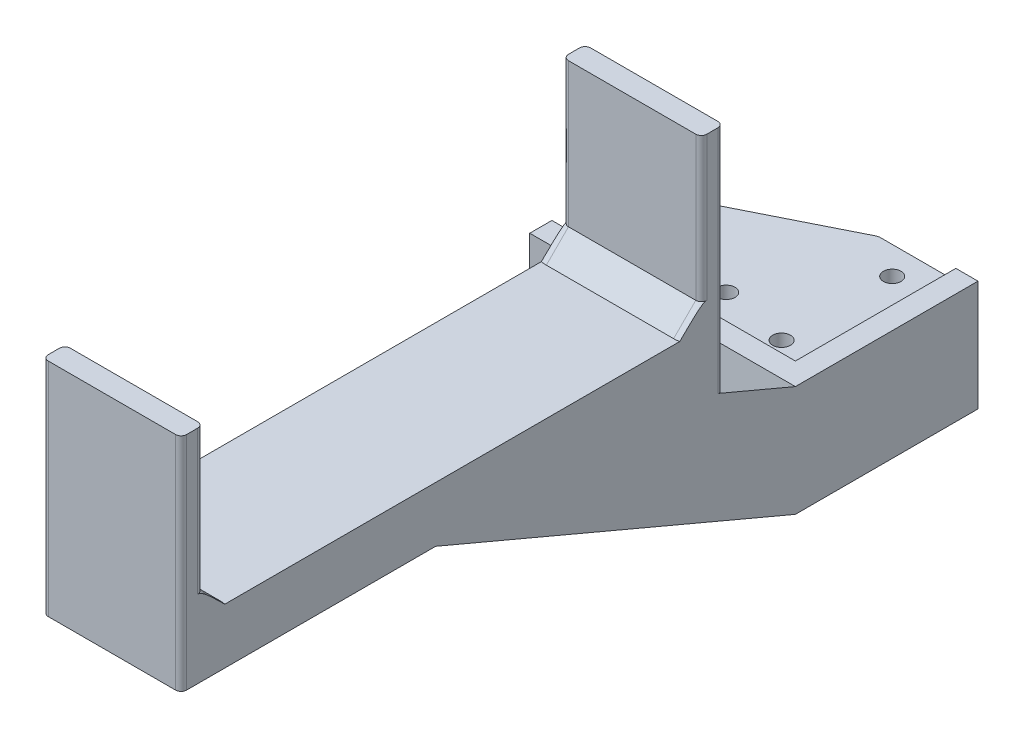
SolidWorks part; units mm, degrees
ref_plane "正面" through (0, 0, 0) normal (0, 0, 1) x (1, 0, 0)
ref_plane "平面" through (0, 0, 0) normal (0, 1, 0) x (1, 0, 0)
ref_plane "右側面" through (0, 0, 0) normal (1, 0, 0) x (0, 0, -1)
sketch "ｽｹｯﾁ1" plane through (0, 0, 0) normal (0, 1, 0) x (1, 0, 0)
  line L0 (7.5, 30) -> (7.5, 0) construction
  line L1 (0, 0) -> (15, 0)
  line L2 (0, 0) -> (0, 30)
  line L3 (0, 30) -> (15, 30)
  line L4 (15, 0) -> (15, 30)
  line L5 (0, 0) -> (-30, 0)
  line L6 (0, 0) -> (0, 15)
  line L7 (0, 15) -> (-30, 15)
  line L8 (-30, 0) -> (-30, 15)
  line L9 (-30, 7.5) -> (0, 7.5) construction
  line L10 (-30, 15) -> (0, 30)
  circle A0 centre (7.5, 5) radius 1.6
  circle A1 centre (-5, 7.5) radius 1.6
  circle A2 centre (-25, 7.5) radius 1.6
  circle A3 centre (7.5, 25) radius 1.6
  dimension "D5" = 3.2
  dimension "D6" = 3.2
  dimension "D7" = 3.2
  dimension "D8" = 3.2
  dimension "D1" = 30
  dimension "D2" = 15
  dimension "D3" = 15
  dimension "D4" = 30
  dimension "D9" = 20
  dimension "D10" = 5
  dimension "D11" = 5
  dimension "D12" = 5
extrude "ﾎﾞｽ - 押し出し1" add sketch "ｽｹｯﾁ1" along normal mid plane 20 contours L8 L5 L2 L7 A2 A1 | L10 L7 L2 | L1 L4 L3 L2 A3 A0 region at (7.5, 0, -15) region at (-15, 0, -7.5) region at (-10, 0, -20)
fillet "ﾌｨﾚｯﾄ1" radius 1.75 2 edges at (0, 0, -30) (-30, 0, -15)
sketch "ｽｹｯﾁ2" plane through (0, 0, 0) normal (0, 0, 1) x (1, 0, 0)
  line L1 (-30, 5) -> (15, 5)
  line L2 (-30, 5) -> (-30, -5)
  line L3 (-30, -5) -> (15, -5)
  line L4 (-30, -10) -> (15, -10)
  line L5 (15, -10) -> (15, 10)
  line L6 (15, 10) -> (-30, 10)
  line L7 (-30, 10) -> (-30, -10)
  line L8 (-30, -10) -> (15, -10)
  line L9 (15, -10) -> (15, 10)
  line L10 (15, 10) -> (-30, 10)
  line L11 (-30, 10) -> (-30, -10)
  line L12 (15, 5) -> (15, -5)
  line M8 (15, -10) -> (15, 10)
  line M10 (-30, 10) -> (-30, -10)
  dimension "D2" = 5
  dimension "D3" = 5
  dimension "D1" = 0
extrude "ｶｯﾄ - 押し出し1" cut sketch "ｽｹｯﾁ2" against normal blind 100 contours L3 L1 M10 M8 region at (-7.5, 0, 0)
sketch "ｽｹｯﾁ3" plane through (0, 0, 0) normal (0, 0, 1) x (1, 0, 0)
  line L1 (-30, 10) -> (15, 10)
  line L2 (-30, 10) -> (-30, -10)
  line L3 (-30, -10) -> (15, -10)
  line L4 (15, 10) -> (15, -10)
extrude "ﾎﾞｽ - 押し出し2" add sketch "ｽｹｯﾁ3" along normal blind 3
sketch "ｽｹｯﾁ4" plane through (15, 0, 0) normal (1, 0, 0) x (0, 0, -1)
  line L5 (-3, 10) -> (30, 10)
  line L6 (-3, 10) -> (-3, -10)
  line L7 (-3, -10) -> (30, -10)
  line L8 (30, 10) -> (30, -10)
extrude "ﾎﾞｽ - 押し出し3" add sketch "ｽｹｯﾁ4" along normal blind 3
sketch "ｽｹｯﾁ5" plane through (0, 10, 0) normal (0, 1, 0) x (1, 0, 0)
  line L0 (-30, 3) -> (12, 3)
  line L1 (12, 3) -> (12, 30)
  line L5 (15, 0) -> (15, 30)
  line L6 (-30, 0) -> (15, 0)
  line L7 (-30, 13.9184) -> (-30, 0)
  line L8 (-0.3695, 29.8152) -> (-29.0326, 15.4837)
  line L9 (15, 30) -> (0.4131, 30)
  line L10 (15, 0) -> (15, 30)
  line L11 (-30, 0) -> (15, 0)
  line L12 (-30, 13.9184) -> (-30, 0)
  line L13 (-0.3695, 29.8152) -> (-29.0326, 15.4837)
  line L14 (15, 30) -> (0.4131, 30)
  arc A2 (-29.0326, 15.4837) -> (-30, 13.9184) centre (-28.25, 13.9184) ccw
  arc A3 (0.4131, 30) -> (-0.3695, 29.8152) centre (0.4131, 28.25) ccw
  arc A4 (-29.0326, 15.4837) -> (-30, 13.9184) centre (-28.25, 13.9184) ccw
  arc A5 (0.4131, 30) -> (-0.3695, 29.8152) centre (0.4131, 28.25) ccw
  line M10 (18, 30) -> (0.4131, 30)
  arc M11 (0.4131, 30) -> (-0.3695, 29.8152) centre (0.4131, 28.25) ccw
  line M12 (-0.3695, 29.8152) -> (-29.0326, 15.4837)
  arc M13 (-29.0326, 15.4837) -> (-30, 13.9184) centre (-28.25, 13.9184) ccw
  line M14 (-30, 13.9184) -> (-30, -3)
  circle M17 centre (-25, 7.5) radius 1.6
  circle M18 centre (-5, 7.5) radius 1.6
  circle M19 centre (7.5, 25) radius 1.6
  circle M20 centre (7.5, 5) radius 1.6
  dimension "D2" = 3
  dimension "D3" = 3
  dimension "D1" = 0
extrude "ｶｯﾄ - 押し出し2" cut sketch "ｽｹｯﾁ5" against normal blind 2 contours L0 L1 M10 M11 M12 M13 M14 M17 M19 M20 M18 | L11 L10 L1 L0 M14 M10 region at (-6.3648, 10, -14.5112) region at (-9, 10, -2.4592)
mirror "ﾐﾗｰ1" about plane through (0, 0, 0) normal (0, 1, 0) of "ｶｯﾄ - 押し出し2"
chamfer "面取り1" distance 3 angle 45 2 edges at (-7.5, 8, 0) (15, 8, -15)
chamfer "面取り2" distance 3 angle 45 1 edges at (15, -8, -15)
sketch "ｽｹｯﾁ6" plane through (18, 0, 0) normal (1, 0, 0) x (0, 0, -1)
  line L0 (-3, -10) -> (-68, 17.5)
  line L1 (-68, 17.5) -> (-114, 17.5)
  line L2 (-3, 10) -> (-44.3636, 27.5)
  line L3 (-44.3636, 27.5) -> (-114, 27.5)
  line L4 (-3, 10) -> (-3, -10)
  line L5 (-3, -10) -> (30, -10)
  line L6 (30, -10) -> (30, 10)
  line L7 (30, 10) -> (-3, 10)
  line L8 (-3, 10) -> (-3, -10)
  line L9 (-3, -10) -> (30, -10)
  line L10 (30, -10) -> (30, 10)
  line L11 (30, 10) -> (-3, 10)
  line L12 (-114, 27.5) -> (-114, 17.5)
  line M10 (-3, 10) -> (-3, -10)
  dimension "D2" = 27.5
  dimension "D3" = 10
  dimension "D4" = 65
  dimension "D5" = 46
  dimension "D1" = 0
extrude "ﾎﾞｽ - 押し出し4" add sketch "ｽｹｯﾁ6" against normal blind 25 contours L3 L12 L1 L0 L2 M10 region at (18, 14.9719, 49.2775)
sketch "ｽｹｯﾁ7" plane through (0, 17.5, 0) normal (0, -1, 0) x (1, 0, 0)
  line L0 (-7, 91) -> (-2, 91) construction
  line L2 (-2, 73) -> (13, 73)
  line L3 (-2, 73) -> (-2, 109)
  line L4 (18, 68) -> (18, 114)
  line L5 (18, 114) -> (-7, 114)
  line L6 (-7, 114) -> (-7, 68)
  line L7 (-7, 68) -> (18, 68)
  line L8 (18, 68) -> (18, 114)
  line L9 (18, 114) -> (-7, 114)
  line L10 (-7, 114) -> (-7, 68)
  line L11 (-7, 68) -> (18, 68)
  line L12 (-2, 109) -> (13, 109)
  line L13 (13, 73) -> (13, 109)
  line L14 (-2, 73) -> (13, 109) construction
  line L15 (-2, 109) -> (13, 73) construction
  circle A0 centre (-2, 73) radius 2.45
  circle A1 centre (-2, 109) radius 2.45
  circle A2 centre (13, 109) radius 2.45
  circle A3 centre (13, 73) radius 2.45
  point P2 (5.5, 91)
  point P16 (5.5, 114)
  dimension "D4" = 4.9
  dimension "D5" = 4.9
  dimension "D6" = 4.9
  dimension "D7" = 4.9
  dimension "D2" = 36
  dimension "D3" = 15
  dimension "D1" = 0
extrude "ｶｯﾄ - 押し出し3" cut sketch "ｽｹｯﾁ7" against normal blind 7.5 contours L3 A0 L2 | L2 A0 L3 | L13 A3 L2 | L2 A3 L13 | L12 A2 L13 | L13 A2 L12 | L12 A1 L3 | L3 A1 L12 region at (-0.9602, 17.5, 74.0398) region at (-2.3466, 17.5, 72.6534) region at (11.9602, 17.5, 74.0398) region at (13.3466, 17.5, 72.6534) region at (-2.3466, 17.5, 109.3466) region at (-0.9602, 17.5, 107.9602) region at (11.9602, 17.5, 107.9602) region at (13.3466, 17.5, 109.3466)
fillet "ﾌｨﾚｯﾄ2" radius 1 2 edges at (-7, 22.5, 114) (18, 22.5, 114)
chamfer "面取り4" distance 15 angle 45 1 edges at (-7, 0, 3)
sketch "ｽｹｯﾁ9" plane through (0, 27.5, 0) normal (0, 1, 0) x (1, 0, 0)
  line L0 (18, -44.3636) -> (18, -3) construction
  line L3 (-7, -18) -> (-7, -44.3636) construction
  line L4 (-7, -44.3636) -> (-7, -113) construction
  line L5 (-6, -114) -> (17, -114) construction
  line L6 (18, -113) -> (18, -44.3636) construction
  line L7 (18, -44.3636) -> (18, -16)
  line L10 (-7, -18) -> (-7, -44.3636)
  line L11 (-7, -44.3636) -> (-7, -113)
  line L12 (-6, -114) -> (17, -114)
  line L13 (18, -113) -> (18, -44.3636)
  line L15 (-7, -110) -> (18, -110)
  line L16 (-7, -110) -> (-7, -114)
  line L17 (-7, -114) -> (18, -114)
  line L18 (18, -110) -> (18, -114)
  line L19 (18, -16) -> (-7, -16)
  line L20 (-7, -18) -> (-7, -16)
  arc A0 (-7, -113) -> (-6, -114) centre (-6, -113) ccw construction
  arc A1 (17, -114) -> (18, -113) centre (17, -113) ccw construction
  arc A2 (-7, -113) -> (-6, -114) centre (-6, -113) ccw
  arc A3 (17, -114) -> (18, -113) centre (17, -113) ccw
  line M12 (18, -44.3636) -> (-7, -44.3636)
  dimension "D1" = 4
  dimension "D2" = 94
extrude "ﾎﾞｽ - 押し出し5" add sketch "ｽｹｯﾁ9" against normal up to surface (12 mm away) contours L7 L19 L10 M12 region at (5.5, 27.5, 30.1818) up to face at (0, 18.2692, 22.5455)
sketch "ｽｹｯﾁ11" plane through (0, 27.5, 0) normal (0, 1, 0) x (1, 0, 0)
  line L0 (-7, -16) -> (-7, -113) construction
  line L1 (18, -16) -> (-7, -16)
  line L2 (18, -16) -> (18, -20)
  line L3 (18, -20) -> (-7, -20)
  line L4 (-7, -16) -> (-7, -20)
  line L5 (18, -16) -> (18, -113) construction
  line L6 (18, -110) -> (-7, -110)
  line L7 (18, -110) -> (18, -114)
  line L8 (18, -114) -> (-7, -114)
  line L9 (-7, -110) -> (-7, -114)
  line L10 (-6, -114) -> (17, -114) construction
  line L15 (-7, -16) -> (-7, -113)
  line L16 (-6, -114) -> (17, -114)
  line L17 (18, -113) -> (18, -16)
  line L18 (18, -16) -> (-7, -16)
  line L19 (-7, -16) -> (-7, -113)
  line L20 (-6, -114) -> (17, -114)
  line L21 (18, -113) -> (18, -16)
  line L22 (18, -16) -> (-7, -16)
  arc A2 (-7, -113) -> (-6, -114) centre (-6, -113) ccw
  arc A3 (17, -114) -> (18, -113) centre (17, -113) ccw
  arc A4 (-7, -113) -> (-6, -114) centre (-6, -113) ccw
  arc A5 (17, -114) -> (18, -113) centre (17, -113) ccw
  line M14 (-7, -16) -> (-7, -113)
  arc M15 (-7, -113) -> (-6, -114) centre (-6, -113) ccw
  line M16 (-6, -114) -> (17, -114)
  arc M17 (17, -114) -> (18, -113) centre (17, -113) ccw
  line M18 (18, -113) -> (18, -16)
  line M19 (18, -16) -> (-7, -16)
  dimension "D1" = 4
  dimension "D2" = 0
  dimension "D3" = 4
extrude "ﾎﾞｽ - 押し出し6" add sketch "ｽｹｯﾁ11" along normal blind 30 contours L3 M18 M19 M14 | L6 M18 M14 M15 M16 M17 region at (5.5, 27.5, 18) region at (5.5, 27.5, 111.9923)
fillet "ﾌｨﾚｯﾄ3" radius 1 6 edges at (18, 42.5, 110) (-7, 42.5, 20) (18, 42.5, 20) (-7, 42.5, 110) (-7, 36.5, 16) (18, 36.5, 16)
chamfer "面取り5" distance 4 angle 45 6 edges at (17.7071, 27.5, 110.2929) (-6.7071, 27.5, 110.2929) (5.5, 27.5, 110) (17.7071, 27.5, 19.7071) (-6.7071, 27.5, 19.7071) (5.5, 27.5, 20)
